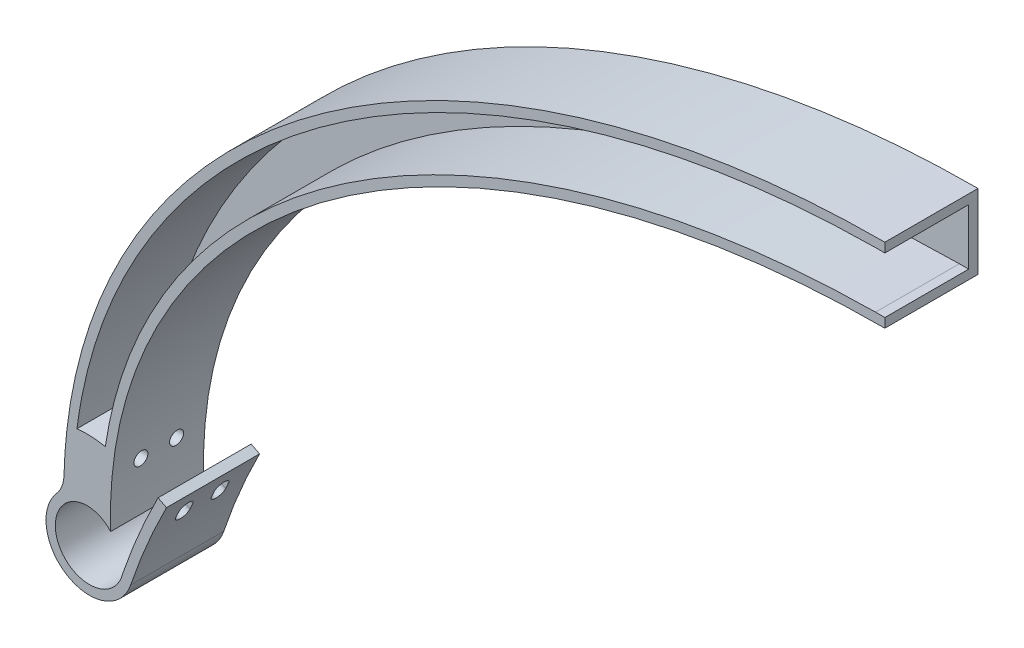
SolidWorks part; units mm, degrees
material "ABS"
ref_plane "Front Plane" through (0, 0, 0) normal (0, 0, 1) x (1, 0, 0)
ref_plane "Top Plane" through (0, 0, 0) normal (0, 1, 0) x (1, 0, 0)
ref_plane "Right Plane" through (0, 0, 0) normal (1, 0, 0) x (0, 0, -1)
sketch "Sketch1" plane through (0, 0, 0) normal (0, 0, 1) x (1, 0, 0)
  line L0 (-307.5, -289.3816) -> (-292.5, -289.3816) construction
  line L1 (-313, -300) -> (-318, -300) construction
  line L2 (-318, -318) -> (-43, -318) construction
  line L3 (-318, -318) -> (-318, -78) construction
  line L4 (-318, -78) -> (-43, -78) construction
  line L5 (-43, -318) -> (-43, -78) construction
  line L6 (-318, -318) -> (-43, -78) construction
  line L7 (-318, -78) -> (-43, -318) construction
  line L8 (-300, -313) -> (-300, -318) construction
  circle A0 centre (-300, -300) radius 10
  circle A1 centre (0, 0) radius 150 construction
  circle A2 centre (-300, -300) radius 13
  ellipse E0 centre (-43, -289.3816) end of major axis (-300, -289.3816) minor radius 189.3816 construction
  ellipse E1 centre (-43, -289.3816) end of major axis (-307.5, -289.3816) minor radius 201.3816 (-43, -88) -> (-307.5, -289.3816) ccw
  ellipse E2 centre (-43, -289.3816) end of major axis (-292.5, -289.3816) minor radius 177.3816 (-292.5, -289.3816) -> (-43, -112) cw
  point P15 (-180.5, -198)
  point P25 (-299.1873, -288.0276)
  point P43 (-299.9797, -287)
  dimension "D2" = 20
  dimension "D3" = 300
  dimension "D5" = 100
  dimension "D6" = 26
  dimension "D9" = 5
  dimension "D1" = 300
  dimension "D4" = 300
  dimension "D7" = 275
  dimension "D8" = 240
  dimension "D10" = 15
  dimension "D11" = 12
  dimension "D12" = 12
sketch "Sketch2" plane through (0, 0, 0) normal (0, 0, 1) x (1, 0, 0)
  line L0 (-43, -289.3816) -> (-306.971, -276.6512) construction
  line L1 (-292.434, -293.4612) -> (-307.566, -293.4612) construction
  line L2 (-292.4554, -292.7993) -> (-292.9764, -276.6978) construction
  line L3 (-306.7301, -271.657) -> (-291.8265, -272.3758) construction
  line L4 (-306.7301, -271.657) -> (-307.2118, -281.6454) construction
  line L5 (-307.2118, -281.6454) -> (-292.3082, -282.3642) construction
  line L6 (-291.8265, -272.3758) -> (-292.3082, -282.3642) construction
  line L7 (-306.7301, -271.657) -> (-292.3082, -282.3642) construction
  line L8 (-307.2118, -281.6454) -> (-291.8265, -272.3758) construction
  line L9 (-292.434, -293.4612) -> (-299.2434, -300.6539) construction
  line L10 (-299.2434, -300.6539) -> (-288.5443, -303.2091) construction
  line L11 (-307.566, -293.4612) -> (-300, -300) construction
  line L12 (-300, -300) -> (-290.0814, -298.7264) construction
  line L13 (-290.0814, -298.7264) -> (-290.7705, -277.4325) construction
  line L14 (-288.5443, -303.2091) -> (-283.3591, -288.0575) construction
  line L15 (-43, -289.3816) -> (-290.919, -269.4442) construction
  line L16 (-274.4361, -277.7752) -> (-277.1478, -276.3849)
  line L17 (-96.9466, -368.7781) -> (-274.4361, -277.7752) construction
  line L18 (-43, -112) -> (-43, -88)
  line L19 (-96.9466, -368.7781) -> (-277.9411, -284.9625) construction
  line L20 (-290.919, -269.4442) -> (-291.9279, -277.3767) construction
  line L21 (-274.4361, -277.7752) -> (-277.9411, -284.9625) construction
  circle A0 centre (-300, -300) radius 10 construction
  arc A1 (-292.434, -293.4612) -> (-307.566, -293.4612) centre (-300, -300) ccw
  arc A2 (-307.566, -293.4612) -> (-288.5443, -303.2091) centre (-299.2434, -300.6539) ccw
  arc A3 (-309.8358, -291.4996) -> (-285.9755, -305.1219) centre (-299.2434, -300.6539) ccw
  arc A4 (-309.8358, -291.4996) -> (-307.4465, -285.3313) centre (-317.2735, -285.0717) ccw
  arc A5 (-307.566, -293.4612) -> (-290.0814, -298.7264) centre (-300, -300) ccw construction
  arc A7 (-309.8358, -291.4996) -> (-285.6264, -303.906) centre (-299.2434, -300.6539) ccw construction
  arc A8 (-290.0814, -298.7264) -> (-288.9254, -269.6045) centre (-87.6806, -292.177) cw construction
  arc A9 (-288.5443, -303.2091) -> (-277.1478, -276.3849) centre (-96.9466, -368.7781) cw
  arc A10 (-285.9755, -305.1219) -> (-274.4361, -277.7752) centre (-96.9466, -368.7781) cw
  ellipse E0 centre (-43, -289.3816) end of major axis (-307.5, -289.3816) minor radius 201.3816 (-43, -88) -> (-307.4465, -285.3313) ccw
  ellipse E1 centre (-43, -289.3816) end of major axis (-292.5, -289.3816) minor radius 177.3816 (-292.434, -293.4612) -> (-43, -112) cw
  ellipse E2 centre (-43, -289.3816) end of major axis (-307.5, -289.3816) minor radius 201.3816 (-43, -88) -> (-307.5, -289.3816) ccw construction
  ellipse E4 centre (-43, -289.3816) end of major axis (206.5, -289.3816) minor radius 177.3816 (-43, -112) -> (-292.5, -289.3816) ccw construction
  point P1 (-299.5192, -277.0106)
  dimension "D1" = 5
  dimension "D3" = 11
  dimension "D7" = 95.464
  dimension "D11" = 202.5067
  dimension "D2" = 10
  dimension "D4" = 60
  dimension "D6" = 228.152
  dimension "D8" = 95.46
  dimension "D9" = 2
  dimension "D10" = 20
  dimension "D5" = 3
extrude "Boss-Extrude1" add sketch "Sketch2" along normal blind 3
sketch "Sketch3" plane through (0, 0, 3) normal (0, 0, 1) x (1, 0, 0)
  line L0 (-46, -109.0127) -> (-46, -91.0131) construction
  line L1 (-300, -300) -> (-298.6836, -270.0289) construction
  line L2 (-274.4361, -277.7752) -> (-277.1478, -276.3849)
  line L3 (-43, -112) -> (-43, -88)
  line L4 (-274.4361, -277.7752) -> (-277.1478, -276.3849)
  line L5 (-43, -112) -> (-43, -88)
  line L6 (-46, -91.0131) -> (-43, -91.0131)
  line L7 (-46, -109.0127) -> (-46, -88) construction
  line L8 (-46, -109.0127) -> (-43, -109.0127)
  arc A0 (-294.1273, -270.5804) -> (-303.2706, -270.1788) centre (-300, -300) ccw
  arc A6 (-309.8358, -291.4996) -> (-307.4465, -285.3313) centre (-317.2735, -285.0717) ccw
  arc A7 (-309.8358, -291.4996) -> (-285.9755, -305.1219) centre (-299.2434, -300.6539) ccw
  arc A8 (-274.4361, -277.7752) -> (-285.9755, -305.1219) centre (-96.9466, -368.7781) ccw
  arc A9 (-277.1478, -276.3849) -> (-288.5443, -303.2091) centre (-96.9466, -368.7781) ccw
  arc A10 (-307.566, -293.4612) -> (-288.5443, -303.2091) centre (-299.2434, -300.6539) ccw
  arc A11 (-292.434, -293.4612) -> (-307.566, -293.4612) centre (-300, -300) ccw
  arc A12 (-309.8358, -291.4996) -> (-307.4465, -285.3313) centre (-317.2735, -285.0717) ccw
  arc A13 (-309.8358, -291.4996) -> (-285.9755, -305.1219) centre (-299.2434, -300.6539) ccw
  arc A14 (-274.4361, -277.7752) -> (-285.9755, -305.1219) centre (-96.9466, -368.7781) ccw
  arc A15 (-277.1478, -276.3849) -> (-288.5443, -303.2091) centre (-96.9466, -368.7781) ccw
  arc A16 (-307.566, -293.4612) -> (-288.5443, -303.2091) centre (-299.2434, -300.6539) ccw
  arc A17 (-292.434, -293.4612) -> (-307.566, -293.4612) centre (-300, -300) ccw
  ellipse E2 centre (-43, -289.3816) end of major axis (-307.5, -289.3816) minor radius 201.3816 (-43, -88) -> (-307.4465, -285.3313) ccw
  ellipse E3 centre (-43, -289.3816) end of major axis (-292.5, -289.3816) minor radius 177.3816 (-43, -112) -> (-292.434, -293.4612) ccw
  ellipse E4 centre (-43, -289.3816) end of major axis (-307.5, -289.3816) minor radius 201.3816 (-43, -88) -> (-307.4465, -285.3313) ccw
  ellipse E5 centre (-43, -289.3816) end of major axis (-292.5, -289.3816) minor radius 177.3816 (-43, -112) -> (-292.434, -293.4612) ccw
  spline S0 degree 1 poles (-46, -109.0127) (-295.4324, -293.5582) knots 0 0 1 1 construction
  spline S1 degree 3 poles (-46, -109.0127) (-54.2816, -109.0829) (-70.8715, -109.8071) (-103.6553, -113.5736) (-143.3806, -122.5716) (-187.1812, -139.8353) (-225.429, -162.9198) (-256.6348, -190.9686) (-279.5603, -222.9339) (-289.5962, -248.3466) (-293.5435, -266.3009) (-295.2874, -278.2093) (-295.6187, -287.8027) (-295.4324, -293.5582) knots -1.558874 -1.558874 -1.558874 -1.558874 -1.460007 -1.36114 -1.163405 -0.965671 -0.767936 -0.570202 -0.372468 -0.174733 -0.135411 -0.072046 0.023001 0.023001 0.023001 0.023001 only from (-46, -109.0127) to (-294.1273, -270.5804)
  spline S2 degree 1 poles (-43, -91) (-304.4475, -285.4106) knots 0 0 1 1 construction
  spline S3 degree 3 poles (-43, -91) (-43.7493, -91) (-45.0001, -91.0041) (-53.4701, -91.0779) (-69.6547, -91.7637) (-101.9745, -95.3663) (-142.7289, -104.6505) (-187.8554, -122.7415) (-227.5058, -147.079) (-260.1925, -176.7195) (-284.7103, -210.5205) (-297.6092, -241.099) (-302.3066, -262.5403) (-303.9367, -275.243) (-304.3466, -281.5913) (-304.4475, -285.4106) knots -1.570796 -1.570796 -1.570796 -1.570796 -1.562215 -1.556495 -1.473879 -1.376961 -1.183126 -0.98929 -0.795455 -0.60162 -0.407784 -0.213949 -0.116729 -0.078083 -0.020114 -0.020114 -0.020114 -0.020114 only from (-46, -91.0131) to (-303.2706, -270.1788)
  point P29 (-295.4324, -293.5582)
  point P32 (0, 0)
  ellipse M11 centre (-43, -289.3816) end of major axis (-307.5, -289.3816) minor radius 201.3816 (-43, -88) -> (-307.4465, -285.3313) ccw
  arc M12 (-307.4465, -285.3313) -> (-309.8358, -291.4996) centre (-317.2735, -285.0717) cw
  arc M13 (-309.8358, -291.4996) -> (-285.9755, -305.1219) centre (-299.2434, -300.6539) ccw
  arc M14 (-285.9755, -305.1219) -> (-274.4361, -277.7752) centre (-96.9466, -368.7781) cw
  line M15 (-274.4361, -277.7752) -> (-277.1478, -276.3849)
  arc M16 (-277.1478, -276.3849) -> (-288.5443, -303.2091) centre (-96.9466, -368.7781) ccw
  arc M17 (-288.5443, -303.2091) -> (-307.566, -293.4612) centre (-299.2434, -300.6539) cw
  arc M18 (-307.566, -293.4612) -> (-292.434, -293.4612) centre (-300, -300) cw
  ellipse M19 centre (-43, -289.3816) end of major axis (-292.5, -289.3816) minor radius 177.3816 (-292.434, -293.4612) -> (-43, -112) cw
  line M20 (-43, -112) -> (-43, -88)
  dimension "D4" = 30
  dimension "D1" = 0
  dimension "D2" = 3
  dimension "D3" = 3
extrude "Boss-Extrude2" add sketch "Sketch3" along normal blind 27 contours S3 L6 L5 L8 S1 A0 M11 M12 M13 M14 M15 M16 M17 M18 M19 M20 region at (-281.0402, -291.0965, 3)
ref_plane "Plane1" through (-278.0441, 13.4091, 0) normal (-0.9988, 0.0482, 0) x (-0.0482, -0.9988, 0)
sketch "Sketch4" plane through (-278.0441, 13.4091, 0) normal (-0.9988, 0.0482, 0) x (-0.0482, -0.9988, 0)
  line L0 (291.117, 0) -> (291.117, 7) construction
  line L1 (291.117, 23) -> (291.117, 30) construction
  line L2 (291.117, 11.5) -> (291.117, 18.5) construction
  line L4 (89.9692, 0) -> (299.8099, 0)
  line L5 (299.8099, 0) -> (299.8099, 30)
  line L6 (299.8099, 30) -> (89.9692, 30)
  line L7 (89.9692, 30) -> (89.9692, 0)
  line L8 (89.9692, 0) -> (299.8099, 0) construction
  line L9 (299.8099, 0) -> (299.8099, 30) construction
  line L10 (299.8099, 30) -> (89.9692, 30) construction
  line L11 (89.9692, 30) -> (89.9692, 0) construction
  circle A0 centre (291.117, 20.75) radius 2.25
  circle A1 centre (291.117, 9.25) radius 2.25
  point P14 (0, 0)
  dimension "D2" = 4.5
  dimension "D1" = 0
extrude "Cut-Extrude1" cut sketch "Sketch4" along normal through all and the other way up to next
ref_plane "Plane2" through (-112.2757, 54.7524, 0) normal (-0.8988, 0.4383, 0) x (-0.4383, -0.8988, 0)
sketch "Sketch5" plane through (-112.2757, 54.7524, 0) normal (-0.8988, 0.4383, 0) x (-0.4383, -0.8988, 0)
  line L0 (376.9567, 20.75) -> (378.9567, 20.75) construction
  line L1 (376.9567, 23) -> (378.9567, 23)
  line L2 (376.9567, 18.5) -> (378.9567, 18.5)
  line L3 (376.9567, 9.25) -> (378.9567, 9.25) construction
  line L4 (376.9567, 11.5) -> (378.9567, 11.5)
  line L5 (376.9567, 7) -> (378.9567, 7)
  line L6 (377.9567, 30) -> (377.9567, 23) construction
  line L7 (377.9567, 18.5) -> (377.9567, 11.5) construction
  line L8 (377.9567, 7) -> (377.9567, 0) construction
  line L10 (369.9603, 0) -> (399.5979, 0)
  line L11 (369.9603, 30) -> (369.9603, 0)
  line L12 (399.5979, 30) -> (369.9603, 30)
  line L13 (399.5979, 0) -> (399.5979, 30)
  line L14 (369.9603, 0) -> (399.5979, 0) construction
  line L15 (369.9603, 30) -> (369.9603, 0) construction
  line L16 (399.5979, 30) -> (369.9603, 30) construction
  line L17 (399.5979, 0) -> (399.5979, 30) construction
  arc A0 (376.9567, 23) -> (376.9567, 18.5) centre (376.9567, 20.75) ccw
  arc A1 (378.9567, 18.5) -> (378.9567, 23) centre (378.9567, 20.75) ccw
  arc A2 (376.9567, 11.5) -> (376.9567, 7) centre (376.9567, 9.25) ccw
  arc A3 (378.9567, 7) -> (378.9567, 11.5) centre (378.9567, 9.25) ccw
  point P2 (377.9567, 20.75)
  point P7 (377.9567, 9.25)
  point P26 (0, 0)
  dimension "D2" = 4.5
  dimension "D3" = 2
  dimension "D1" = 0
extrude "Cut-Extrude2" cut sketch "Sketch5" along normal up to next and the other way through all
